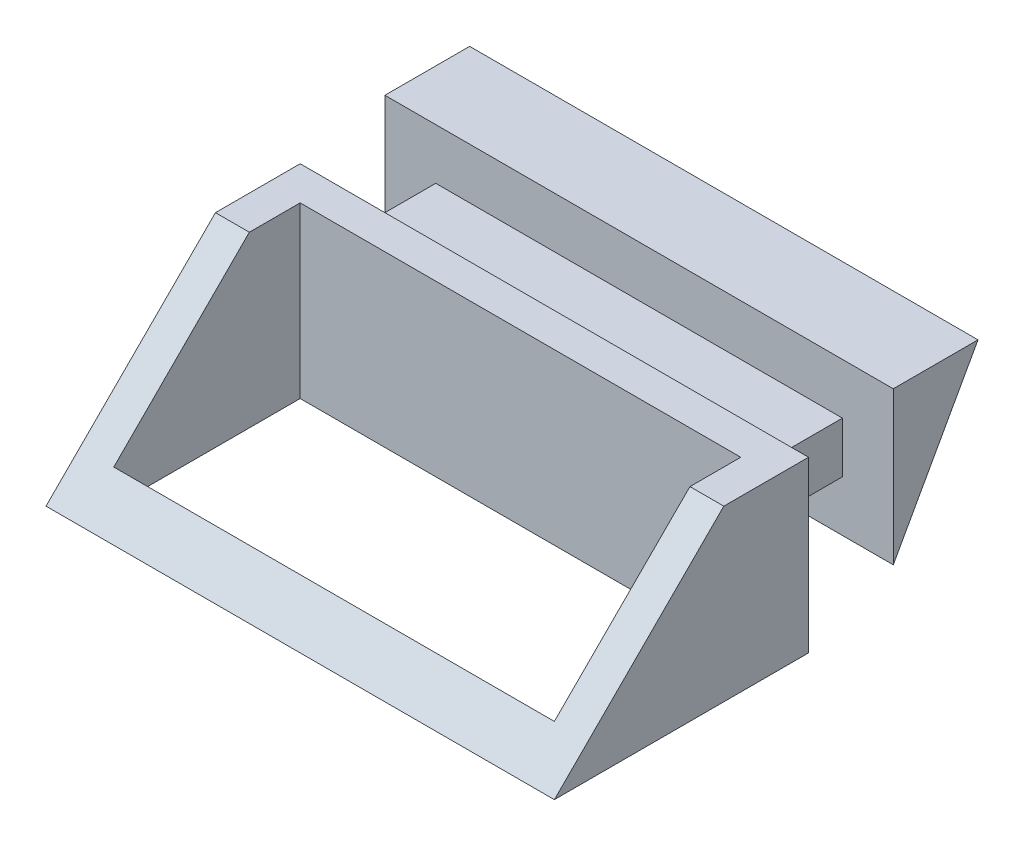
SolidWorks part; units mm, degrees
material "Alumina"
ref_plane "Front Plane" through (0, 0, 0) normal (0, 0, 1) x (1, 0, 0)
ref_plane "Top Plane" through (0, 0, 0) normal (0, 1, 0) x (1, 0, 0)
ref_plane "Right Plane" through (0, 0, 0) normal (1, 0, 0) x (0, 0, -1)
sketch "Sketch12" plane through (0, 0, 0) normal (0, 1, 0) x (1, 0, 0)
  line L1 (-15, -7.5) -> (15, -7.5)
  line L2 (-15, -7.5) -> (-15, 7.5)
  line L3 (-15, 7.5) -> (15, 7.5)
  line L4 (15, -7.5) -> (15, 7.5)
  line L5 (-15, -7.5) -> (15, 7.5) construction
  line L6 (-15, 7.5) -> (15, -7.5) construction
  point P0 (0, 0)
  dimension "D1" = 15
  dimension "D2" = 30
extrude "Boss-Extrude4" add sketch "Sketch12" along normal blind 10
chamfer "Chamfer1" distance 10 angle 45 1 edges at (0, 10, 7.5)
sketch "Sketch14" plane through (0, 0, -7.5) normal (0, 0, -1) x (-1, 0, 0)
  line L0 (-15, 10) -> (-15, 0) construction
  line L1 (-12, 5) -> (12, 5)
  line L2 (-12, 5) -> (-12, 8)
  line L3 (-12, 8) -> (12, 8)
  line L4 (12, 5) -> (12, 8)
  line L5 (15, 10) -> (15, 0) construction
  line L6 (-15, 10) -> (15, 10) construction
  dimension "D1" = 3
  dimension "D2" = 3
  dimension "D3" = 2
  dimension "D4" = 3
extrude "Boss-Extrude5" add sketch "Sketch14" along normal blind 5
sketch "Sketch15" plane through (0, 0, -12.5) normal (0, 0, -1) x (-1, 0, 0)
  line L0 (-12, 8) -> (-12, 5) construction
  line L1 (-15, 2) -> (15, 2)
  line L2 (-15, 2) -> (-15, 11)
  line L3 (-15, 11) -> (15, 11)
  line L4 (15, 2) -> (15, 11)
  line L5 (-12, 5) -> (12, 5) construction
  line L6 (12, 8) -> (-12, 8) construction
  line L7 (12, 5) -> (12, 8) construction
  dimension "D1" = 3
  dimension "D2" = 3
  dimension "D3" = 3
  dimension "D4" = 3
extrude "Boss-Extrude6" add sketch "Sketch15" along normal blind 5
sketch "Sketch17" plane through (-15, 0, 0) normal (-1, 0, 0) x (0, 0, 1)
  line L0 (-12.5, 2) -> (-17.5, 11)
  line L1 (-17.5, 11) -> (-17.5, 2)
  line L2 (-17.5, 2) -> (-12.5, 2)
extrude "Cut-Extrude10" cut sketch "Sketch17" against normal through all both and the other way through all
sketch "Sketch18" plane through (0, 0, 0) normal (0, -1, 0) x (1, 0, 0)
  line L0 (-15, -7.5) -> (-15, 7.5) construction
  line L1 (-13, -5.5) -> (13, -5.5)
  line L2 (-13, -5.5) -> (-13, 5.5)
  line L3 (-13, 5.5) -> (13, 5.5)
  line L4 (13, -5.5) -> (13, 5.5)
  line L5 (15, -7.5) -> (-15, -7.5) construction
  line L6 (-15, 7.5) -> (15, 7.5) construction
  line L7 (15, 7.5) -> (15, -7.5) construction
  dimension "D1" = 2
  dimension "D2" = 2
  dimension "D3" = 2
  dimension "D4" = 2
extrude "Cut-Extrude11" cut sketch "Sketch18" against normal through all both and the other way through all
scale "Scale1" scale about centroid uniform scaling yes scale factor 6
